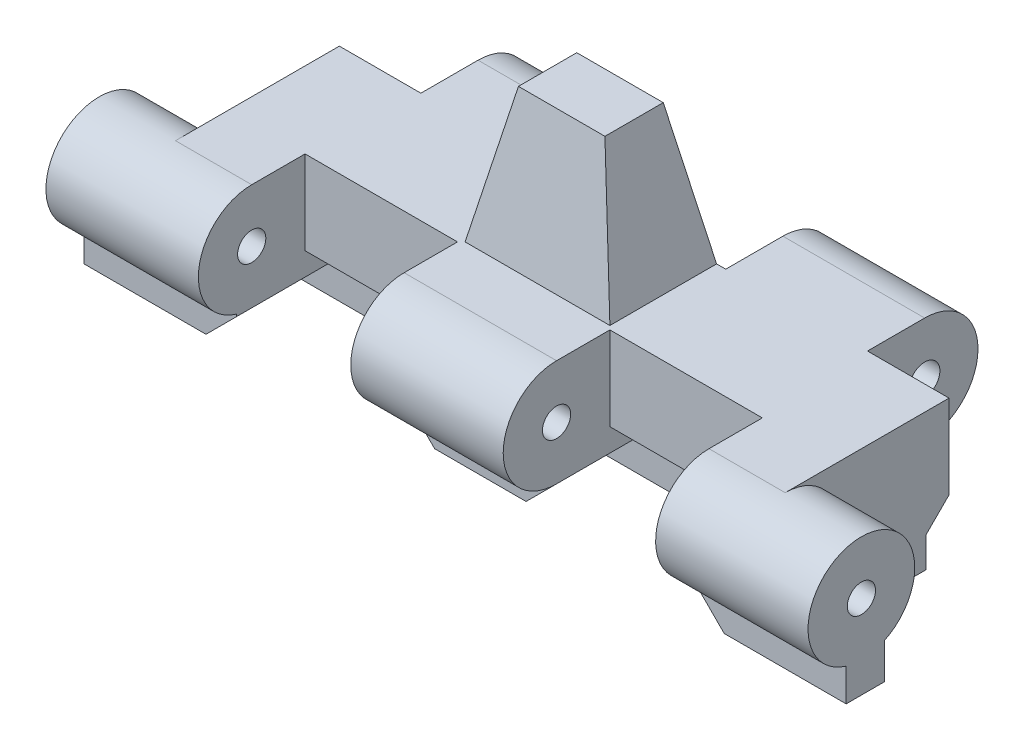
SolidWorks part; units mm, degrees
ref_plane "Front Plane" through (0, 0, 0) normal (0, 0, 1) x (1, 0, 0)
ref_plane "Top Plane" through (0, 0, 0) normal (0, 1, 0) x (1, 0, 0)
ref_plane "Right Plane" through (0, 0, 0) normal (1, 0, 0) x (0, 0, -1)
sketch "Sketch1" plane through (0, 0, 0) normal (1, 0, 0) x (0, 0, -1)
  line L0 (-155.8607, 0) -> (7637.1742, 0) construction
  line L1 (0, -155.8607) -> (0, 7637.1742) construction
  line L3 (7.25, -3.5) -> (-7.25, -3.5)
  line L4 (7.25, -3.5) -> (7.25, 3.5)
  line L5 (7.25, 3.5) -> (-7.25, 3.5)
  line L6 (-7.25, -3.5) -> (-7.25, 3.5)
  line L7 (7.25, -3.5) -> (-7.25, 3.5) construction
  line L8 (7.25, 3.5) -> (-7.25, -3.5) construction
  circle A0 centre (-7.25, 0) radius 3.5
  circle A1 centre (7.25, 0) radius 3.5
  point P4 (0, 0)
  dimension "D1" = 14.5
  dimension "D2" = 7
extrude "Boss-Extrude2" add sketch "Sketch1" along normal blind 40 contours L6 A0 | L4 A1
sketch "Sketch3" plane through (40, 0, 0) normal (1, 0, 0) x (0, 0, -1)
  circle A0 centre (-7.25, 0) radius 3.5
extrude "Boss-Extrude3" add sketch "Sketch3" along normal blind 5
sketch "Sketch4" plane through (0, 0, 0) normal (-1, 0, 0) x (0, 0, 1)
  circle A0 centre (7.25, 0) radius 3.5
extrude "Boss-Extrude4" add sketch "Sketch4" along normal blind 5
sketch "Sketch5" plane through (0, 3.5, 0) normal (0, 1, 0) x (1, 0, 0)
  line L0 (-1000, 0) -> (49000, 0) construction
  line L1 (-1000, 3.5) -> (49000, 3.5) construction
  line L3 (-1000, -3.75) -> (49000, -3.75) construction
  line L4 (5.35, -1000) -> (5.35, 49000) construction
  line L5 (5, -1000) -> (5, 49000) construction
  line L7 (14.65, -1000) -> (14.65, 49000) construction
  line L8 (15, -1000) -> (15, 49000) construction
  line L9 (25, -1000) -> (25, 49000) construction
  line L10 (25.35, -1000) -> (25.35, 49000) construction
  line L11 (34.65, -1000) -> (34.65, 49000) construction
  line L12 (35, -1000) -> (35, 49000) construction
  line L15 (-5, -3.75) -> (-5, -10.75) construction
  line L17 (-5, -10.75) -> (45, -10.75) construction
  line L18 (5, -10.75) -> (15, -10.75)
  line L19 (5, -10.75) -> (5, -3.75)
  line L20 (5, -3.75) -> (15, -3.75)
  line L21 (15, -10.75) -> (15, -3.75)
  line L22 (40, 10.75) -> (0, 10.75) construction
  line L23 (5.35, 3.5) -> (0, 3.5)
  line L24 (5.35, 3.5) -> (5.35, 10.75)
  line L25 (5.35, 10.75) -> (0, 10.75)
  line L26 (0, 3.5) -> (0, 10.75)
  line L27 (0, 10.75) -> (0, 7.25) construction
  line L28 (40, 7.25) -> (40, -7.25) construction
  line L29 (25, -3.75) -> (35, -3.75)
  line L30 (25, -3.75) -> (25, -10.75)
  line L31 (25, -10.75) -> (35, -10.75)
  line L32 (35, -3.75) -> (35, -10.75)
  line L33 (14.65, 10.75) -> (25.35, 10.75)
  line L34 (14.65, 10.75) -> (14.65, 3.5)
  line L35 (14.65, 3.5) -> (25.35, 3.5)
  line L36 (25.35, 10.75) -> (25.35, 3.5)
  line L37 (34.65, 10.75) -> (40, 10.75)
  line L38 (34.65, 10.75) -> (34.65, 3.5)
  line L39 (34.65, 3.5) -> (40, 3.5)
  line L40 (40, 10.75) -> (40, 3.5)
  dimension "D1" = 3.5
  dimension "D2" = 10
  dimension "D3" = 0.35
  dimension "D4" = 9.3
  dimension "D5" = 0.35
  dimension "D6" = 10
  dimension "D7" = 0.35
  dimension "D8" = 9.3
  dimension "D9" = 0.35
extrude "Cut-Extrude2" cut sketch "Sketch5" against normal through all both and the other way through all
sketch "Sketch6" plane through (-5, 0, 0) normal (-1, 0, 0) x (0, 0, 1)
  circle A0 centre (7.25, 0) radius 0.925
  dimension "D1" = 1.85
extrude "Cut-Extrude3" cut sketch "Sketch6" against normal through all both and the other way through all
sketch "Sketch7" plane through (5.35, 0, 0) normal (-1, 0, 0) x (0, 0, 1)
  circle A0 centre (-7.25, 0) radius 1
  dimension "D1" = 2
extrude "Cut-Extrude4" cut sketch "Sketch7" against normal through all both and the other way through all
sketch "Sketch8" plane through (0, 3.5, 0) normal (0, 1, 0) x (1, 0, 0)
  line L0 (-1000, 0) -> (49000, 0) construction
  line L1 (20, -996.5) -> (20, 49003.5) construction
  line L2 (25.35, 3.5) -> (14.65, 3.5) construction
  line L4 (24.75, -3.5) -> (15.25, -3.5)
  line L5 (24.75, -3.5) -> (24.75, 3.5)
  line L6 (24.75, 3.5) -> (15.25, 3.5)
  line L7 (15.25, -3.5) -> (15.25, 3.5)
  line L8 (24.75, -3.5) -> (15.25, 3.5) construction
  line L9 (24.75, 3.5) -> (15.25, -3.5) construction
  point P4 (20, 0)
  point P8 (20, 3.5)
  dimension "D1" = 9.5
extrude "Boss-Extrude5" add sketch "Sketch8" along normal blind 9
chamfer "Chamfer1" distance 9 angle 10 2 edges at (20, 12.5, 3.5) (20, 12.5, -3.5)
chamfer "Chamfer2" distance 9 angle 12 2 edges at (15.25, 12.5, 0) (24.75, 12.5, 0)
sketch "Sketch9" plane through (0, -3.5, 0) normal (0, -1, 0) x (-1, 0, 0)
  line L0 (0, -1010.5) -> (0, 48989.5) construction
  line L1 (-5, -10.75) -> (5, -10.75) construction
  line L2 (-10, -989.5) -> (-10, 49010.5) construction
  line L3 (-5.35, 10.75) -> (-14.65, 10.75) construction
  line L4 (-20, -1010.5) -> (-20, 48989.5) construction
  line L5 (-25, -10.75) -> (-15, -10.75) construction
  line L6 (-30, -989.5) -> (-30, 49010.5) construction
  line L7 (-25.35, 10.75) -> (-34.65, 10.75) construction
  line L8 (-40, -1010.5) -> (-40, 48989.5) construction
  line L9 (-45, -10.75) -> (-35, -10.75) construction
  line L10 (-1000, 0) -> (49000, 0) construction
  line L11 (-1034.0112, -3.5) -> (48965.9888, -3.5) construction
  line L13 (-1035.7562, 3.5) -> (48964.2438, 3.5) construction
  line L14 (0, -7.25) -> (-5, -7.25)
  line L15 (0, -7.25) -> (0, -3.75)
  line L16 (0, -3.75) -> (-5, -3.75)
  line L17 (-5, -7.25) -> (-5, -3.75)
  line L18 (-5.35, 7.25) -> (-14.65, 7.25)
  line L19 (-5.35, 7.25) -> (-5.35, 3.5)
  line L20 (-5.35, 3.5) -> (-14.65, 3.5)
  line L21 (-14.65, 7.25) -> (-14.65, 3.5)
  line L22 (-15, -7.25) -> (-25, -7.25)
  line L23 (-15, -7.25) -> (-15, -3.75)
  line L24 (-15, -3.75) -> (-25, -3.75)
  line L25 (-25, -7.25) -> (-25, -3.75)
  line L26 (-25.35, 7.25) -> (-34.65, 7.25)
  line L27 (-25.35, 7.25) -> (-25.35, 3.5)
  line L28 (-25.35, 3.5) -> (-34.65, 3.5)
  line L29 (-34.65, 7.25) -> (-34.65, 3.5)
  line L30 (-35, -7.25) -> (-40, -7.25)
  line L31 (-35, -7.25) -> (-35, -3.5)
  line L32 (-35, -3.5) -> (-40, -3.5)
  line L33 (-40, -7.25) -> (-40, -3.5)
  line L52 (-5, -7.25) -> (-5, -10.75) construction
  line L53 (-5, -8.25) -> (5, -8.25)
  line L54 (-5, -8.25) -> (-5, -5.75)
  line L55 (-5, -5.75) -> (5, -5.75)
  line L56 (5, -8.25) -> (5, -5.75)
  line L57 (5, -10.75) -> (5, -3.75) construction
  line L58 (-35, -10.75) -> (-35, -7.25) construction
  line L59 (-35, -8.25) -> (-45, -8.25)
  line L60 (-35, -8.25) -> (-35, -5.75)
  line L61 (-35, -5.75) -> (-45, -5.75)
  line L62 (-45, -8.25) -> (-45, -5.75)
  line L63 (-45, -3.75) -> (-45, -10.75) construction
  line L66 (-40, 2) -> (0, 2)
  line L67 (-40, 2) -> (-40, -2)
  line L68 (-40, -2) -> (0, -2)
  line L69 (0, 2) -> (0, -2)
  line L70 (0, -2) -> (-5, -2)
  line L71 (0, -2) -> (0, -3.75)
  line L72 (0, -3.75) -> (-5, -3.75)
  line L73 (-5, -2) -> (-5, -3.75)
  line L74 (-35, -3.5) -> (-40, -3.5)
  line L75 (-35, -3.5) -> (-35, -2)
  line L76 (-35, -2) -> (-40, -2)
  line L77 (-40, -3.5) -> (-40, -2)
  line L78 (-5.35, 3.5) -> (-14.65, 3.5)
  line L79 (-5.35, 3.5) -> (-5.35, 2)
  line L80 (-5.35, 2) -> (-14.65, 2)
  line L81 (-14.65, 3.5) -> (-14.65, 2)
  line L82 (-25.35, 3.5) -> (-34.65, 3.5)
  line L83 (-25.35, 3.5) -> (-25.35, 2)
  line L84 (-25.35, 2) -> (-34.65, 2)
  line L85 (-34.65, 3.5) -> (-34.65, 2)
  line L86 (-15, -3.75) -> (-25, -3.75)
  line L87 (-15, -3.75) -> (-15, -2)
  line L88 (-15, -2) -> (-25, -2)
  line L89 (-25, -3.75) -> (-25, -2)
  point P5 (0, -10.75)
  point P10 (-10, 10.75)
  point P15 (-20, -10.75)
  point P20 (-30, 10.75)
  point P25 (-40, -10.75)
  dimension "D1" = 3.5
  dimension "D2" = 3.5
  dimension "D3" = 2.5
  dimension "D4" = 2.25
  dimension "D5" = 2.5
  dimension "D6" = 2.25
  dimension "D7" = 4
  dimension "D8" = 2
extrude "Boss-Extrude7" add sketch "Sketch9" along normal blind 2 and the other way blind 2
sketch "Sketch14" plane through (5.35, 0, 0) normal (-1, 0, 0) x (0, 0, 1)
  line L0 (-3.5, -3.5) -> (-4.625, -5.5)
  line L1 (-2, -5.5) -> (-7.25, -5.5) construction
chamfer "Chamfer7" distance 2 angle 45 22 edges at (5, -5.5, 5.125) (5.35, -5.5, -4.625) (14.65, -5.5, -4.625) (25.35, -5.5, -4.625) (34.65, -5.5, -4.625) (35, -5.5, 5.125) (25, -5.5, 4.625) (15, -5.5, 4.625) (34.65, -4.5, -2) (34.65, -4.5, -7.25) (25.35, -4.5, -7.25) (14.65, -4.5, -7.25) (5.35, -4.5, -2) (5.35, -4.5, -7.25) (15, -4.5, 7.25) (25, -4.5, 2) (25, -4.5, 7.25) (35, -4.5, 2) (14.65, -4.5, -2) (25.35, -4.5, -2) (15, -4.5, 2) (5, -4.5, 2)
chamfer "Chamfer9" distance 1.5 angle 45 5 edges at (37.325, -3.5, -3.5) (20, -3.5, -3.5) (2.675, -3.5, -3.5) (10, -3.5, 3.75) (30, -3.5, 3.75)
